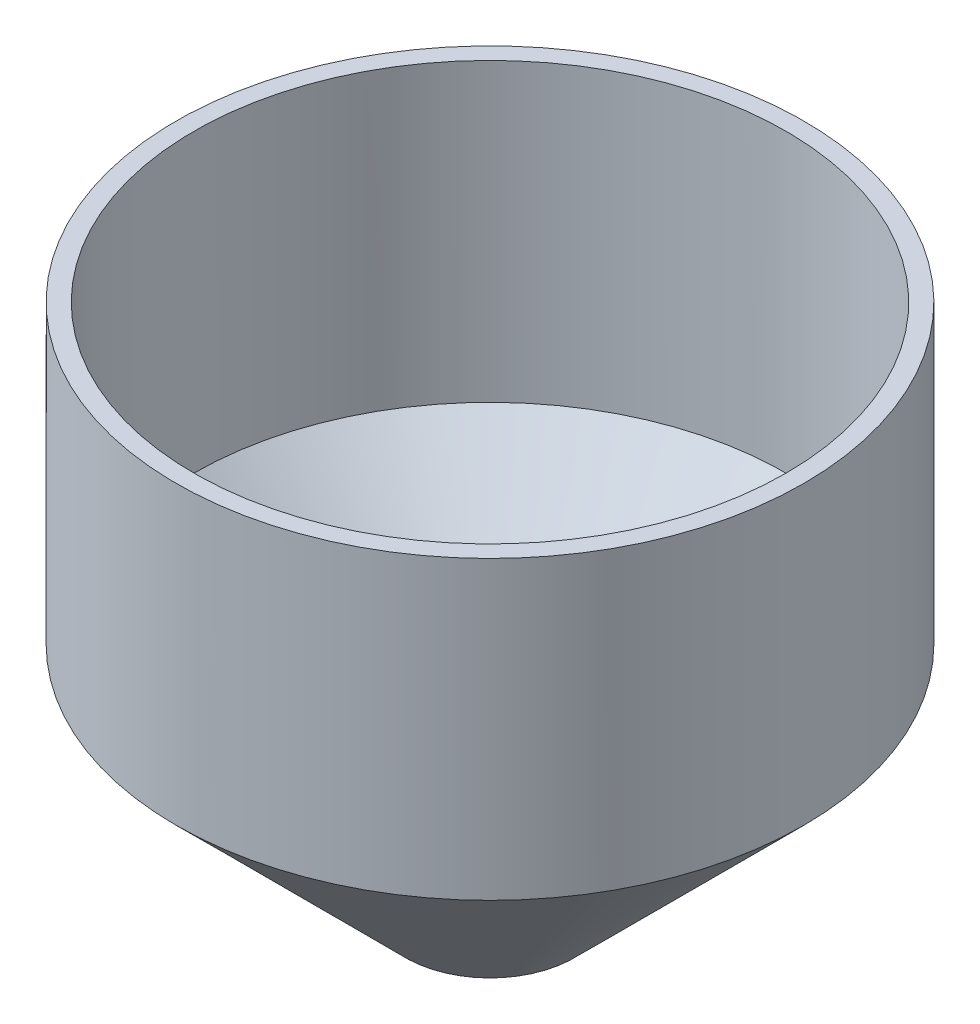
SolidWorks part; units mm, degrees
ref_plane "Front Plane" through (0, 0, 0) normal (0, 0, 1) x (1, 0, 0)
ref_plane "Top Plane" through (0, 0, 0) normal (0, 1, 0) x (1, 0, 0)
ref_plane "Right Plane" through (0, 0, 0) normal (1, 0, 0) x (0, 0, -1)
sketch "Sketch2" plane through (0, 0, 0) normal (0, 0, 1) x (1, 0, 0)
  line L0 (21.2, 20) -> (21.2, 0)
  line L1 (21.2, 0) -> (5.7, -15.5)
  line L2 (5.7, -15.5) -> (4.5, -15.5)
  line L3 (4.5, -15.5) -> (20, 0)
  line L4 (20, 0) -> (20, 20)
  line L5 (20, 20) -> (21.2, 20)
  line L6 (0, -1000) -> (0, 49000) construction
  line L7 (4.5, -15.5) -> (10.3857, -15.5) construction
  dimension "D1" = 1.2
  dimension "D2" = 20
  dimension "D3" = 45
  dimension "D4" = 20
  dimension "D5" = 4.5
revolve "Revolve2" add sketch "Sketch2" angle 360 about L6
